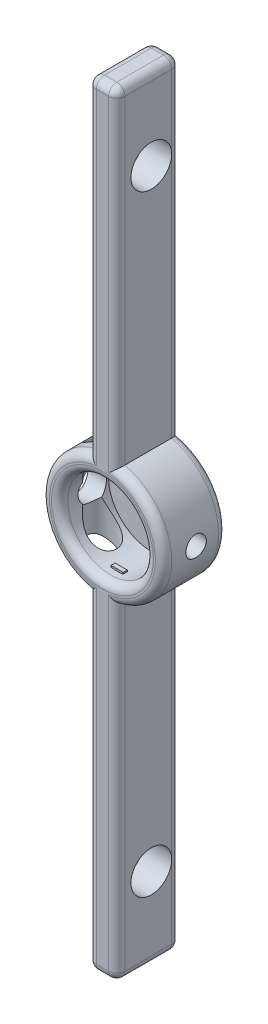
SolidWorks part; units mm, degrees
ref_plane "Front Plane" through (0, 0, 0) normal (1, 0, 0) x (0, 1, 0)
ref_plane "Top Plane" through (0, 0, 0) normal (0, 0, 1) x (0, 1, 0)
ref_plane "Right Plane" through (0, 0, 0) normal (0, 1, 0) x (-1, 0, 0)
sketch "Sketch4" plane through (0, 0, 0) normal (0, 0, 1) x (0, 1, 0)
  line L1 (0, -55) -> (0, 55) construction
  line L9 (-95, 3.5) -> (-95, -3.5)
  line L15 (14.586, 3.5) -> (95, 3.5)
  line L16 (-55, 0) -> (55, 0) construction
  line L17 (14.586, -3.5) -> (95, -3.5)
  line L18 (95, 3.5) -> (95, -3.5)
  line L19 (-14.586, -3.5) -> (-95, -3.5)
  line L20 (-14.586, 3.5) -> (-95, 3.5)
  arc A0 (-14.586, -3.5) -> (14.586, -3.5) centre (0, 0) ccw
  arc A1 (14.586, 3.5) -> (-14.586, 3.5) centre (0, 0) ccw
  dimension "D1" = 30
  dimension "D2" = 3.5
  dimension "D3" = 95
extrude "Boss-Extrude1" add sketch "Sketch4" along normal blind 15.5
sketch "Sketch5" plane through (0, 0, 0) normal (0, 0, -1) x (1, 0, 0)
  circle A0 centre (0, 0) radius 10.5
  dimension "D1" = 21
extrude "Cut-Extrude1" cut sketch "Sketch5" against normal blind 2
sketch "Sketch6" plane through (3.5, 0, 0) normal (1, 0, 0) x (0, 1, 0)
  line L0 (0, -8.525) -> (0, 8.525) construction
  line L1 (75, 7) -> (75, 26.9755) construction
  line L2 (75, 2) -> (94.3035, 2) construction
  line L3 (16.5, 0) -> (-16.5, 0) construction
  circle A0 centre (75, 7) radius 5
  circle A1 centre (-75, 7) radius 5
  circle A5 centre (93.5568, 24.3985) radius 5
  circle A6 centre (98.3828, 29.6055) radius 1.25
  circle A7 centre (88.7308, 29.6055) radius 1.25
  circle A8 centre (70.174, 12.207) radius 1.2
  circle A9 centre (79.826, 12.207) radius 1.2
  circle A10 centre (-70.174, 12.207) radius 1.2
  circle A11 centre (-79.826, 12.207) radius 1.2
  dimension "D1" = 10
  dimension "D3" = 2
  dimension "D6" = 2.4
  dimension "D2" = 75
  dimension "D4" = 5.207
  dimension "D5" = 4.826
  dimension "D7" = 5.207
  dimension "D8" = 4.826
extrude "Cut-Extrude5" cut sketch "Sketch6" against normal through all contours A0 | A1 region at (3.5, 75, 7) region at (3.5, -75, 7)
sketch "Sketch7" plane through (-3.5, 0, 0) normal (-1, 0, 0) x (0, -1, 0)
  line L0 (-79.826, 13.407) -> (-90.3926, 13.407) construction
  line L2 (-95, 15.5) -> (-14.586, 15.5) construction
  circle A0 centre (-70.174, 12.207) radius 1.2 construction
  circle A1 centre (-79.826, 12.207) radius 1.2 construction
  circle A2 centre (-70.174, 12.207) radius 1.2
  circle A3 centre (-79.826, 12.207) radius 1.2
  circle A4 centre (70.174, 12.207) radius 1.2 construction
  circle A5 centre (79.826, 12.207) radius 1.2 construction
  circle A6 centre (70.174, 12.207) radius 1.2
  circle A7 centre (79.826, 12.207) radius 1.2
  dimension "D1" = 2.093
extrude "Cut-Extrude6" cut sketch "Sketch7" against normal blind 6
sketch "Sketch17" plane through (0, 0, 15.5) normal (0, 0, 1) x (1, 0, 0)
  circle A0 centre (0, 0) radius 10.5 construction
  circle A1 centre (0, 0) radius 10.5
extrude "Cut-Extrude7" cut sketch "Sketch17" against normal blind 12
sketch "Sketch18" plane through (0, 0, 0) normal (1, 0, 0) x (0, 1, 0)
  line L0 (0, -8.525) -> (0, 8.525) construction
  line L1 (-10.5, 0) -> (10.5, 0) construction
  circle A0 centre (0, 7.5) radius 2.5
  dimension "D1" = 5
  dimension "D2" = 7.5
extrude "Cut-Extrude8" cut sketch "Sketch18" against normal through all both and the other way through all
sketch "Sketch19" plane through (0, 0, 0) normal (0, 1, 0) x (-1, 0, 0)
  line L0 (-3.5, 15.5) -> (-15, 15.5) construction
  line L2 (0, 8.525) -> (0, -8.525) construction
  circle A0 centre (7.5, 8) radius 3.5
  dimension "D3" = 7
  dimension "D1" = 7.5
  dimension "D2" = 7.5
extrude "Cut-Extrude9" cut sketch "Sketch19" against normal through all both and the other way through all
sketch "Sketch20" plane through (0, 0, 0) normal (1, 0, 0) x (0, 1, 0)
  circle A1 centre (0, 7.5) radius 3.5
  dimension "D1" = 7
extrude "Cut-Extrude11" cut sketch "Sketch20" against normal through all
fillet "Fillet1" radius 2 21 edges at (-3.5, -54.793, 0) (0, -95, 0) (3.5, -54.793, 0) (15, 0, 0) (3.5, 54.793, 0) (0, 95, 0) (-3.5, 54.793, 0) (-15, 0, 0) (-3.5, 54.793, 15.5) (0, 95, 15.5) (3.5, 54.793, 15.5) (15, 0, 15.5) (3.5, -54.793, 15.5) (0, -95, 15.5) (-3.5, -54.793, 15.5) (-15, 0, 15.5) (-3.5, -95, 7.75) (3.5, -95, 7.75) (-3.5, 95, 7.75) (3.5, 95, 7.75) (10.5, 0, 15.5)
ref_plane "Plane4" through (0, 12, 0) normal (0, 1, 0) x (-1, 0, 0)
sketch "Sketch23" plane through (0, 12, 0) normal (0, 1, 0) x (-1, 0, 0)
  line L0 (5.5503, 10.9067) -> (0, 10.9067) construction
  line L1 (0, 8.525) -> (0, -8.525) construction
  line L2 (-1.5, 10.9067) -> (1.4826, 10.9067)
  line L3 (-1.5, 10.9067) -> (-1.5, 11.9082)
  line L4 (1.4826, 10.9067) -> (1.4826, 11.9082)
  line L5 (-1.5, 11.9082) -> (1.4826, 11.9082)
  line L6 (-1.5, 13.5) -> (-1.5, 2) construction
  circle A0 centre (7.5, 8) radius 3.5 construction
extrude "Boss-Extrude2" add sketch "Sketch23" against normal blind 2
mirror "Mirror2" about plane through (0, 0, 0) normal (0, 1, 0) of "Boss-Extrude2"
sketch "Sketch24" plane through (0, 0, 0) normal (0, 1, 0) x (-1, 0, 0)
  line L0 (-3.5, 13.5) -> (-3.5, 2) construction
  line L1 (-1.5, 15.5) -> (1.5, 15.5) construction
  line L2 (3.5, 13.5) -> (3.5, 2) construction
  line L3 (-3.5, 13.5) -> (-3.5, 2)
  line L4 (-1.5, 15.5) -> (1.5, 15.5)
  line L5 (3.5, 13.5) -> (3.5, 2)
  arc A0 (1.5, 0) -> (3.5, 2) centre (1.5, 2) ccw construction
  arc A1 (1.5, 0) -> (3.5, 2) centre (1.5, 2) ccw construction
  arc A2 (-3.5, 2) -> (-1.5, 0) centre (-1.5, 2) ccw construction
  arc A3 (-1.5, 15.5) -> (-3.5, 13.5) centre (-1.5, 13.5) ccw construction
  arc A4 (3.5, 13.5) -> (1.5, 15.5) centre (1.5, 13.5) ccw construction
  arc A5 (3.5, 13.5) -> (1.5, 15.5) centre (1.5, 13.5) ccw construction
  arc A6 (1.5, 0) -> (3.5, 2) centre (1.5, 2) ccw
  arc A7 (1.5, 0) -> (3.5, 2) centre (1.5, 2) ccw
  arc A8 (-3.5, 2) -> (-1.5, 0) centre (-1.5, 2) ccw
  arc A9 (-1.5, 15.5) -> (-3.5, 13.5) centre (-1.5, 13.5) ccw
  arc A10 (3.5, 13.5) -> (1.5, 15.5) centre (1.5, 13.5) ccw
  arc A11 (3.5, 13.5) -> (1.5, 15.5) centre (1.5, 13.5) ccw
